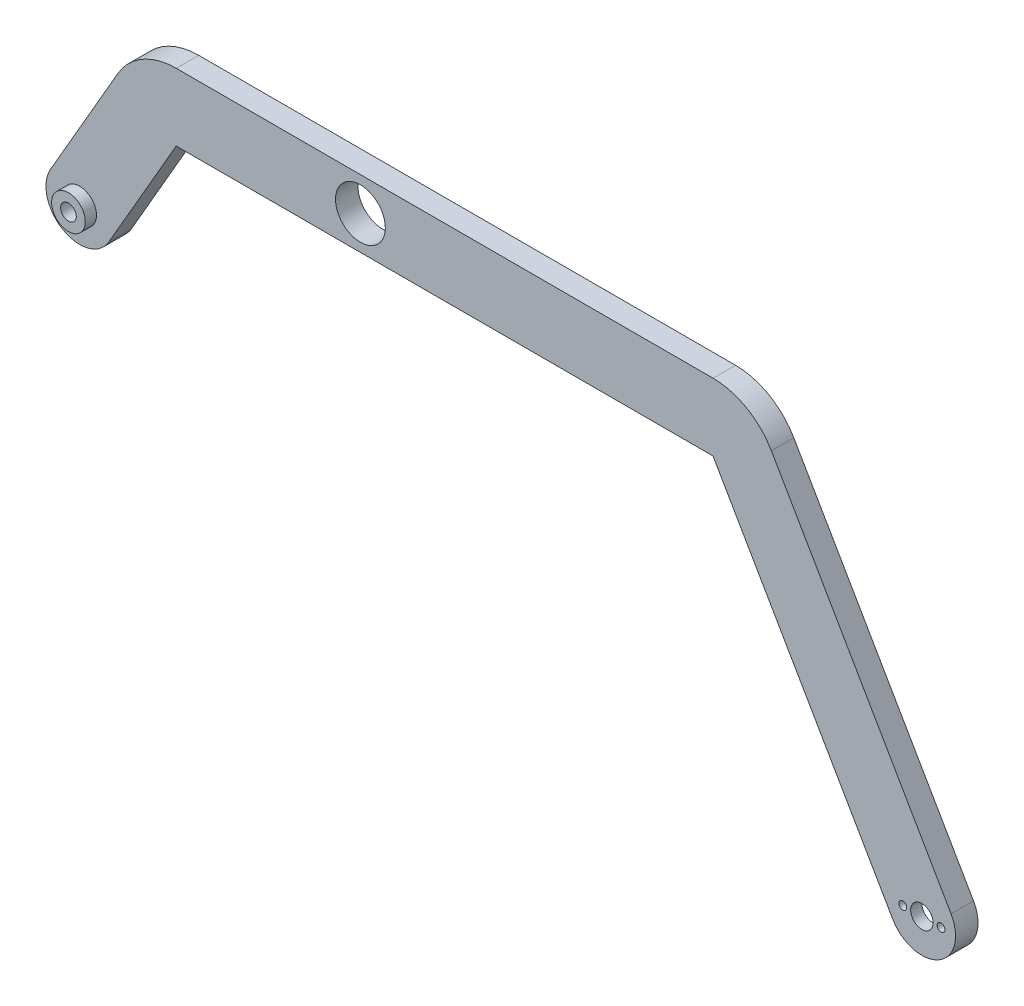
SolidWorks part; units mm, degrees
ref_plane "Front Plane" through (0, 0, 0) normal (0, 0, 1) x (1, 0, 0)
ref_plane "Top Plane" through (0, 0, 0) normal (0, 1, 0) x (1, 0, 0)
ref_plane "Right Plane" through (0, 0, 0) normal (1, 0, 0) x (0, 0, -1)
sketch "Sketch1" plane through (0, 0, 0) normal (0, 0, 1) x (1, 0, 0)
  line L0 (0, -15) -> (0, 15) construction
  line L4 (-82.0096, -15) -> (-112.0096, -66.9615)
  line L6 (-137.9904, -51.9615) -> (-107.9904, 0)
  line L7 (262.9904, -138.5641) -> (182.9904, 0)
  line L9 (157.0096, -15) -> (237.0096, -153.5641)
  line L10 (0, 15) -> (157.0096, 15)
  line L11 (0, -15) -> (157.0096, -15)
  line L12 (0, 15) -> (-82.0096, 15)
  line L13 (0, -15) -> (-82.0096, -15)
  line L14 (237.0096, -153.5641) -> (262.9904, -138.5641) construction
  line L15 (-137.9904, -51.9615) -> (-112.0096, -66.9615) construction
  arc A1 (-107.9904, 0) -> (-82.0096, 15) centre (-82.0096, -15) cw
  arc A2 (182.9904, 0) -> (157.0096, 15) centre (157.0096, -15) ccw
  arc A6 (237.0096, -153.5641) -> (262.9904, -138.5641) centre (250, -146.0641) ccw
  arc A7 (-137.9904, -51.9615) -> (-112.0096, -66.9615) centre (-125, -59.4615) ccw
  circle A8 centre (258.5, -146.0433) radius 1.75
  circle A9 centre (241.5, -146.0848) radius 1.75
  point P4 (0, 0)
  point P7 (0, -15)
  point P20 (0, 15)
  dimension "D2" = 60
  dimension "D6" = 3.5
  dimension "D7" = 3.5
  dimension "D1" = 30
  dimension "D3" = 250
  dimension "D4" = 160
  dimension "D5" = 125
extrude "Boss-Extrude1" add sketch "Sketch1" along normal blind 10
sketch "Sketch2" plane through (0, 0, 10) normal (0, 0, 1) x (1, 0, 0)
  circle A1 centre (250, -146.0641) radius 5
  circle A2 centre (0, 0) radius 11.0875
  dimension "D1" = 22.175
extrude "Cut-Extrude1" cut sketch "Sketch2" against normal up to surface (10 mm away) up to face at (260.25, -146.0433, 0)
sketch "Sketch3" plane through (0, 0, 0) normal (0, 0, -1) x (-1, 0, 0)
  circle A0 centre (0, 0) radius 12
sketch "Sketch4" plane through (0, 0, 0) normal (0, 0, -1) x (-1, 0, 0)
  circle A0 centre (-250, -146.0641) radius 13
  dimension "D1" = 26
extrude "Cut-Extrude2" cut sketch "Sketch4" against normal offset from surface (5 mm away) 5 up to face at (255, -146.0641, 10)
sketch "Sketch8" plane through (0, 0, 10) normal (0, 0, 1) x (1, 0, 0)
  circle A0 centre (-125, -59.4615) radius 7.5
  dimension "D1" = 15
extrude "Boss-Extrude2" add sketch "Sketch8" along normal blind 5
sketch "Sketch9" plane through (0, 0, 15) normal (0, 0, 1) x (1, 0, 0)
  circle A0 centre (-125, -59.4615) radius 3.5
  dimension "D1" = 7
extrude "Cut-Extrude3" cut sketch "Sketch9" against normal through all
